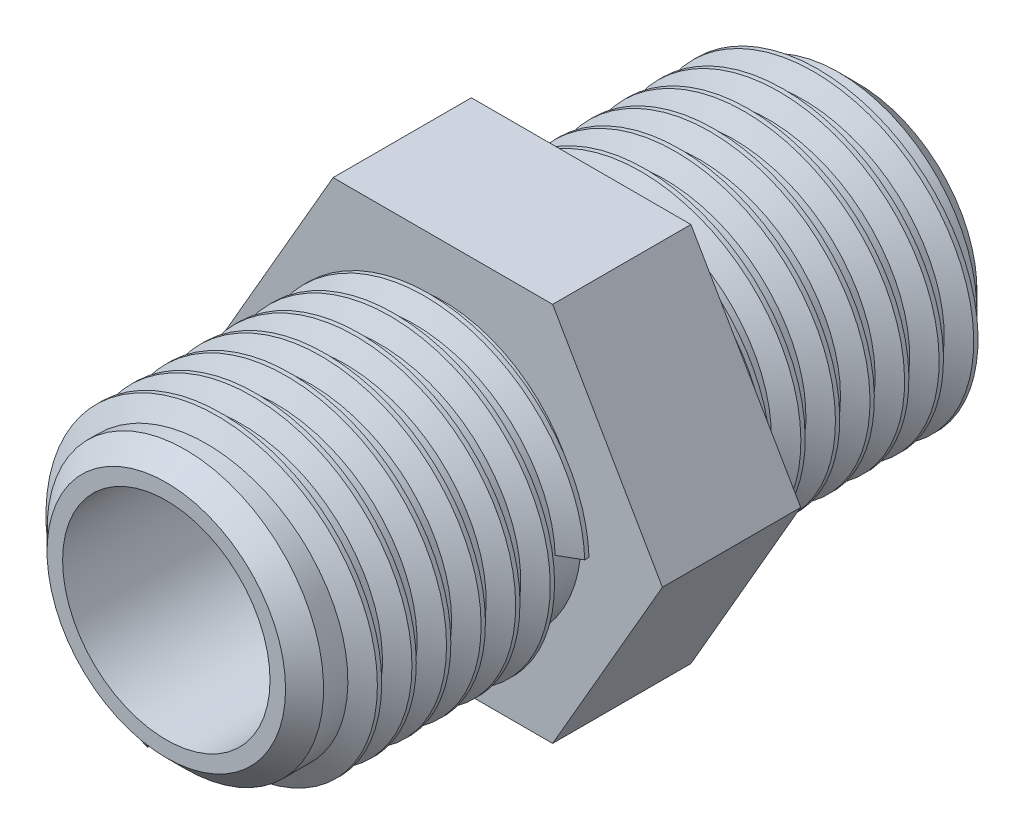
SolidWorks part; units mm, degrees
material "Brass"
ref_plane "Front Plane" through (0, 0, 0) normal (0, 0, 1) x (1, 0, 0)
ref_plane "Top Plane" through (0, 0, 0) normal (0, 1, 0) x (1, 0, 0)
ref_plane "Right Plane" through (0, 0, 0) normal (1, 0, 0) x (0, 0, -1)
sketch "Sketch1" plane through (0, 0, 0) normal (0, 0, 1) x (1, 0, 0)
  line L1 (6.3509, 0) -> (3.1754, 5.5)
  line L2 (3.1754, 5.5) -> (-3.1754, 5.5)
  line L3 (-3.1754, 5.5) -> (-6.3509, 0)
  line L4 (-6.3509, 0) -> (-3.1754, -5.5)
  line L5 (-3.1754, -5.5) -> (3.1754, -5.5)
  line L6 (3.1754, -5.5) -> (6.3509, 0)
  circle A0 centre (0, 0) radius 5.5 construction
  dimension "D1" = 11
extrude "Boss-Extrude1" add sketch "Sketch1" along normal blind 4
sketch "Sketch2" plane through (0, 0, 4) normal (0, 0, 1) x (1, 0, 0)
  circle A0 centre (0, 0) radius 4
extrude "Boss-Extrude2" add sketch "Sketch2" along normal blind 8
sketch "Sketch3" plane through (0, 0, 0) normal (0, 0, -1) x (-1, 0, 0)
  circle A0 centre (0, 0) radius 4
extrude "Boss-Extrude3" add sketch "Sketch3" along normal blind 8
sketch "Sketch4" plane through (0, 0, -8) normal (0, 0, -1) x (-1, 0, 0)
  circle A0 centre (0, 0) radius 2.5
extrude "Cut-Extrude1" cut sketch "Sketch4" against normal through all
sketch "Sketch5" plane through (0, 0, -8) normal (0, 0, -1) x (-1, 0, 0)
  circle A0 centre (0, 0) radius 3
extrude "Cut-Extrude2" cut sketch "Sketch5" against normal blind 6
sketch "Sketch6" plane through (0, 0, 12) normal (0, 0, 1) x (1, 0, 0)
  circle A0 centre (0, 0) radius 3
extrude "Cut-Extrude3" cut sketch "Sketch6" against normal blind 6
chamfer "Chamfer1" distance 0.55 angle 45 2 edges at (-4, 0, -8) (4, 0, 12)
thread "Thread1" pitch 1 method extrude profile "Thread Profile1" start angle 0, offset 0, length 6.7, pitch 1, diameter 8
ref_plane "Plane1" through (4, 0, 4) normal (0, -1, 0) x (1, 0, 0)
sketch "Thread Profile1" plane through (4, 0, 4) normal (0, -1, 0) x (1, 0, 0)
  line L0 (0, 0) -> (0, 1) construction
  line L1 (0, 0) -> (0.5413, 0.3125)
  line L2 (0.5413, 0.3125) -> (0.5413, 0.4375)
  line L3 (0.5413, 0.4375) -> (0, 0.75)
  line L4 (0.5413, 0.375) -> (0, 0.375) construction
  line L11 (0, 0) -> (0, 0.75)
  point P2 (0, 0)
  dimension "Pitch" = 1
  dimension "Profile_Angle" = 60
  dimension "Profile_Land" = 0.125
  dimension "Profile_Height" = 0.5413
thread "Thread2" pitch 1 method extrude profile "Thread Profile2" start angle 0, offset 0, length 6.7, pitch 1, diameter 8
ref_plane "Plane2" through (-4, 0, 0) normal (0, -1, 0) x (-1, 0, 0)
sketch "Thread Profile2" plane through (-4, 0, 0) normal (0, -1, 0) x (-1, 0, 0)
  line L0 (0, 0) -> (0, 1) construction
  line L1 (0, 0) -> (0.5413, 0.3125)
  line L2 (0.5413, 0.3125) -> (0.5413, 0.4375)
  line L3 (0.5413, 0.4375) -> (0, 0.75)
  line L4 (0.5413, 0.375) -> (0, 0.375) construction
  line L11 (0, 0) -> (0, 0.75)
  point P2 (0, 0)
  dimension "Pitch" = 1
  dimension "Profile_Angle" = 60
  dimension "Profile_Land" = 0.125
  dimension "Profile_Height" = 0.5413
